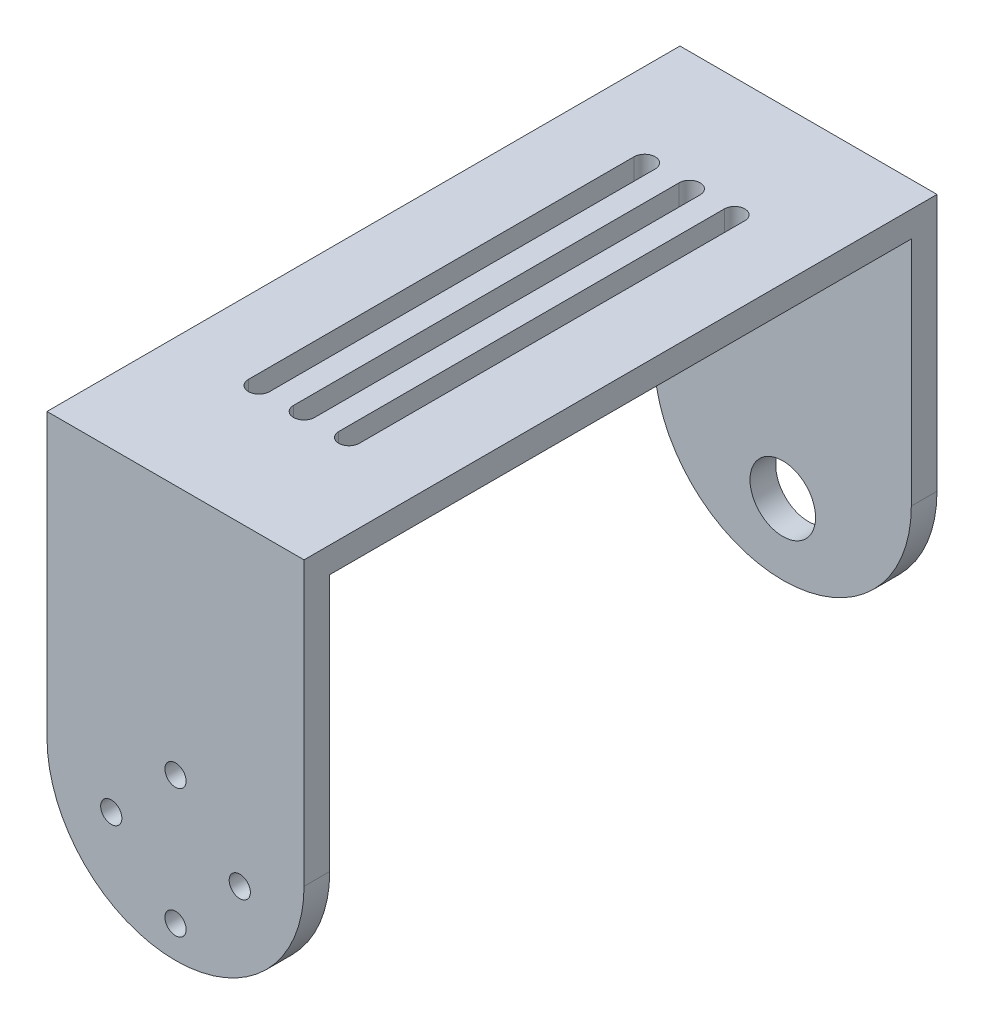
SolidWorks part; units mm, degrees
ref_plane "前视基准面" through (0, 0, 0) normal (0, 0, 1) x (1, 0, 0)
ref_plane "上视基准面" through (0, 0, 0) normal (0, 1, 0) x (1, 0, 0)
ref_plane "右视基准面" through (0, 0, 0) normal (1, 0, 0) x (0, 0, -1)
other "Configuration Table"
sketch "草图1" plane through (0, 0, 0) normal (0, 0, 1) x (1, 0, 0)
  line L0 (-20, 0) -> (-20, -15)
  line L2 (-20, 0) -> (-20, 45)
  line L3 (-20, 45) -> (20, 45)
  line L4 (20, 3.1478) -> (20, 45)
  line L5 (-20, -15) -> (20, -15)
  line L6 (20, -15) -> (20, 3.1478)
  line L7 (0, -10) -> (0, 70.2795) construction
  circle A4 centre (-10, 0) radius 1.65
  circle A5 centre (0, 10) radius 1.65
  circle A6 centre (0, -10) radius 1.65
  circle A7 centre (10, 0) radius 1.65
  circle A8 centre (0, 0) radius 10 construction
  dimension "D1" = 60
  dimension "D2" = 20
  dimension "D3" = 10
  dimension "D4" = 20
  dimension "D5" = 10
  dimension "D6" = 10
  dimension "D7" = 10
  dimension "D8" = 15
extrude "凸台-拉伸1" add sketch "草图1" along normal blind 4
sketch "草图2" plane through (0, 0, 0) normal (0, 0, 1) x (1, 0, 0)
  line L0 (20, -15) -> (20, 45) construction
  line L1 (-20, 45) -> (20, 45)
  line L2 (-20, 45) -> (-20, 49)
  line L3 (-20, 49) -> (20, 49)
  line L4 (20, 45) -> (20, 49)
  dimension "D1" = 4
extrude "凸台-拉伸2" add sketch "草图2" against normal blind 98.5 from surface starting at face at (0, 15, 4)
sketch "草图4" plane through (0, 0, 0) normal (0, 1, 0) x (1, 0, 0)
  line L0 (20, 94.5) -> (20, -4) construction
  line L1 (-20, 94.5) -> (20, 94.5)
  line L2 (-20, 94.5) -> (-20, 90.5)
  line L3 (-20, 90.5) -> (20, 90.5)
  line L4 (20, 94.5) -> (20, 90.5)
  dimension "D1" = 4
extrude "凸台-拉伸3" add sketch "草图4" against normal blind 60 from surface starting at face at (0, 49, -45.25)
sketch "草图6" plane through (0, 0, 0) normal (0, 1, 0) x (1, 0, 0)
  line L0 (7, 46) -> (-46.6066, 46) construction
  line L1 (0, 46) -> (0, 72.2246) construction
  line L2 (-20, 76) -> (29.1586, 76) construction
  line L3 (-20, 16) -> (29.1586, 16) construction
  line L4 (-7, 16) -> (-7, 76) construction
  line L5 (-8.65, 16) -> (-8.65, 76)
  line L6 (-5.35, 16) -> (-5.35, 76)
  line L7 (0, 76) -> (0, 16) construction
  line L8 (1.6345, 76) -> (1.6345, 16)
  line L9 (-1.6345, 76) -> (-1.6345, 16)
  line L10 (7, 76) -> (7, 16) construction
  line L11 (8.5982, 76) -> (8.5982, 16)
  line L12 (5.4018, 76) -> (5.4018, 16)
  circle A2 centre (7, 46) radius 1.65 construction
  circle A4 centre (-7, 46) radius 1.65 construction
  circle A5 centre (0, 46) radius 1.65 construction
  arc A7 (-8.65, 16) -> (-5.35, 16) centre (-7, 16) ccw
  arc A8 (-5.35, 76) -> (-8.65, 76) centre (-7, 76) ccw
  arc A9 (1.6345, 76) -> (-1.6345, 76) centre (0, 76) ccw
  arc A10 (-1.6345, 16) -> (1.6345, 16) centre (0, 16) ccw
  arc A11 (8.5982, 76) -> (5.4018, 76) centre (7, 76) ccw
  arc A12 (5.4018, 16) -> (8.5982, 16) centre (7, 16) ccw
  point P5 (0, 46)
  point P14 (0, 46)
  point P21 (-7, 46)
  point P28 (0, 46)
  point P35 (7, 46)
  dimension "D1" = 30
  dimension "D2" = 3.3
fillet "圆角1" radius 20 4 edges at (-20, -11, -92.5) (20, -11, -92.5) (20, -15, 2) (-20, -15, 2)
extrude "切除-拉伸2" cut sketch "草图6" along normal through all
sketch "草图8" plane through (0, 0, 0) normal (0, 0, 1) x (1, 0, 0)
  circle A0 centre (0, 0) radius 5.1
  dimension "D1" = 10.2
extrude "切除-拉伸3" cut sketch "草图8" against normal blind 10 from surface starting at face at (0, 17.7431, -90.5)
